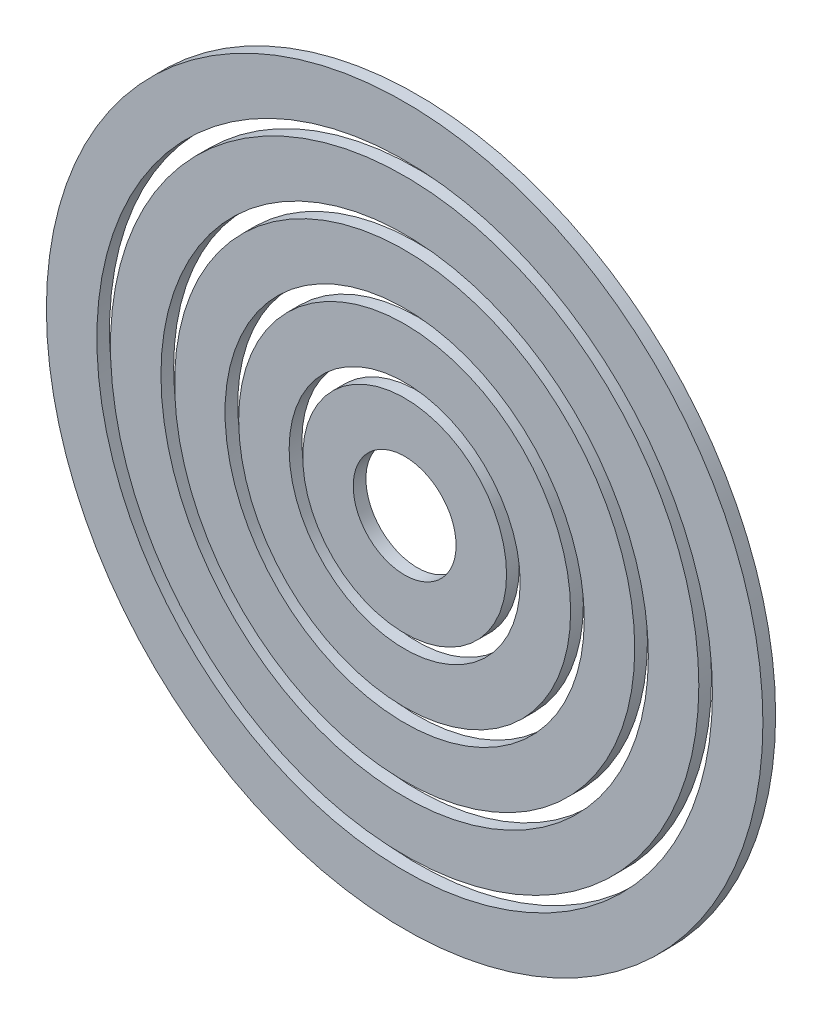
SolidWorks part; units mm, degrees
ref_plane "Front Plane" through (0, 0, 0) normal (0, 0, 1) x (1, 0, 0)
ref_plane "Top Plane" through (0, 0, 0) normal (0, 1, 0) x (1, 0, 0)
ref_plane "Right Plane" through (0, 0, 0) normal (1, 0, 0) x (0, 0, -1)
sketch "Sketch1" plane through (0, 0, 0) normal (0, 0, 1) x (1, 0, 0)
  circle A0 centre (0, 0) radius 15.9
  circle A1 centre (0, 0) radius 8.026
  circle A3 centre (0, 0) radius 25.9
  circle A4 centre (0, 0) radius 35.9
  circle A5 centre (0, 0) radius 45.9
  circle A6 centre (0, 0) radius 55.9
  circle A7 centre (0, 0) radius 48.026
  circle A8 centre (0, 0) radius 38.026
  circle A9 centre (0, 0) radius 28.026
  circle A10 centre (0, 0) radius 18.026
  dimension "D1" = 31.8
  dimension "D3" = 51.8
  dimension "D2" = 7.874
  dimension "D4" = 10
  dimension "D5" = 10
  dimension "D6" = 10
  dimension "D7" = 7.874
extrude "Boss-Extrude1" add sketch "Sketch1" along normal blind 1.9812 contours A6 A7 | A5 A8 | A4 A9 | A3 A10 | A0 A1 region at (-15.4503, 0, 0) region at (-25.1674, 0, 0) region at (-34.8846, 0, 0) region at (-44.6018, 0, 0) region at (-54.3189, 0, 0)
